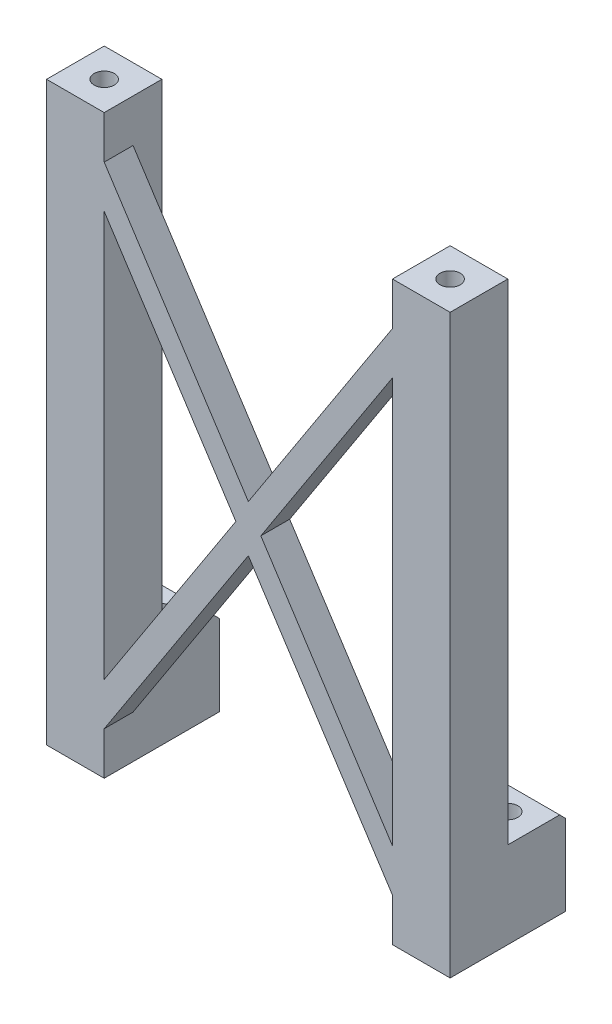
SolidWorks part; units mm, degrees
ref_plane "Alzado" through (0, 0, 0) normal (0, 0, 1) x (1, 0, 0)
ref_plane "Planta" through (0, 0, 0) normal (0, 1, 0) x (1, 0, 0)
ref_plane "Vista lateral" through (0, 0, 0) normal (1, 0, 0) x (0, 0, -1)
sketch "Croquis3" plane through (0, 0, 0) normal (0, 1, 0) x (1, 0, 0)
  line L1 (25, 5) -> (35, 5)
  line L2 (25, 5) -> (25, -5)
  line L3 (25, -5) -> (35, -5)
  line L4 (35, 5) -> (35, -5)
  line L5 (25, 5) -> (35, -5) construction
  line L6 (25, -5) -> (35, 5) construction
  circle A0 centre (30, 0) radius 1.75
  dimension "D1" = 3.5
  dimension "D2" = 30
  dimension "D3" = 10
  dimension "D4" = 10
extrude "Saliente-Extruir1" add sketch "Croquis3" along normal blind 50
sketch "Croquis4" plane through (0, 0, 0) normal (0, 0, 1) x (1, 0, 0)
  line L0 (0, 0) -> (0, 4.0664)
  line L1 (0, 4.0664) -> (25, 42.5554)
  line L3 (25, 50) -> (25, 0) construction
  line L4 (25, 42.5554) -> (25, 35.1546)
  line L5 (25, 35.1546) -> (2.1658, 0)
  line L6 (2.1658, 0) -> (0, 0)
extrude "Saliente-Extruir2" add sketch "Croquis4" along normal up to surface (5 mm away) up to face at (30, 25, 5)
mirror "Simetría1" about plane through (0, 0, 0) normal (0, 1, 0) of bodies 102
sketch "Croquis9" plane through (0, -50, 0) normal (0, -1, 0) x (1, 0, 0)
  line L0 (35, -5) -> (25, -5)
  line L1 (35, -5) -> (35, -15)
  line L2 (25, -5) -> (25, -15)
  line L3 (35, -15) -> (25, -15)
  line L4 (25, -5) -> (35, -15) construction
  circle A0 centre (30, -10) radius 1.75
  dimension "D2" = 3.5
  dimension "D1" = 10
extrude "Saliente-Extruir4" add sketch "Croquis9" against normal blind 15
chamfer "Chaflán1" distance 1 angle 45 1 edges at (30, -35, -15)
mirror "Simetría2" about plane through (0, 0, 0) normal (1, 0, 0) of bodies 106 103
